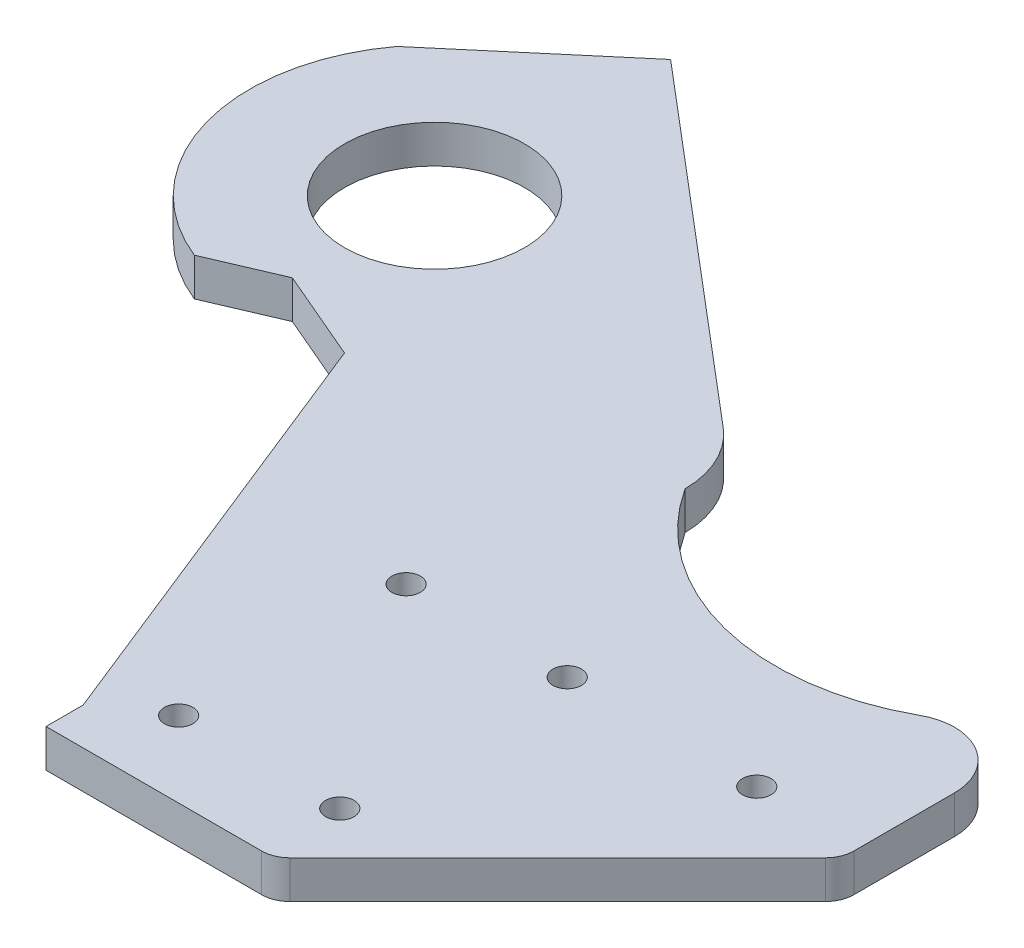
SolidWorks part; units mm, degrees
ref_plane "前视基准面" through (0, 0, 0) normal (0, 0, 1) x (1, 0, 0)
ref_plane "上视基准面" through (0, 0, 0) normal (0, 1, 0) x (1, 0, 0)
ref_plane "右视基准面" through (0, 0, 0) normal (1, 0, 0) x (0, 0, -1)
other "Configuration Table"
sketch "草图2" plane through (0, 0, 0) normal (0, 1, 0) x (1, 0, 0)
  line L0 (0, 0) -> (0, 60)
  line L1 (0, 60) -> (40, 93.9081)
  line L2 (40, 93.9081) -> (80, 60)
  line L3 (80, 60) -> (80, 0)
  line L4 (80, 0) -> (68, 0)
  line L5 (68, 0) -> (68, 42)
  line L6 (68, 42) -> (12, 42) construction
  line L7 (12, 42) -> (12, 0)
  line L8 (12, 0) -> (0, 0)
  line L9 (12, 42) -> (40, 54)
  line L10 (40, 54) -> (68, 42)
  line L11 (40, 93.9081) -> (40, 54) construction
  circle A0 centre (6, 32) radius 1.5
  circle A1 centre (6, 8) radius 1.5
  circle A2 centre (40, 69) radius 9.5
  circle A3 centre (74, 8) radius 1.5
  circle A4 centre (74, 32) radius 1.5
  dimension "D5" = 3
  dimension "D6" = 8
  dimension "D7" = 24
  dimension "D8" = 6
  dimension "D9" = 19
  dimension "D10" = 27
  dimension "D11" = 19
  dimension "D1" = 80
  dimension "D2" = 12
  dimension "D3" = 12
  dimension "D4" = 60
  dimension "D12" = 12
  dimension "D13" = 10
extrude "凸台-拉伸1" add sketch "草图2" along normal blind 4
sketch "草图4" plane through (0, 4, 0) normal (0, 1, 0) x (1, 0, 0)
  line L20 (0, 60) -> (0, 0)
  line L21 (0, 0) -> (12, 0)
  line L22 (12, 0) -> (12, 42)
  line L23 (12, 42) -> (40, 54)
  line L24 (40, 54) -> (68, 42)
  line L25 (68, 42) -> (68, 0)
  line L26 (68, 0) -> (80, 0)
  line L27 (80, 0) -> (80, 60)
  line L28 (80, 60) -> (40, 93.9081)
  line L29 (40, 93.9081) -> (0, 60)
  line L30 (0, 60) -> (0, 0)
  line L31 (0, 0) -> (12, 0)
  line L32 (12, 0) -> (12, 42)
  line L33 (12, 42) -> (40, 54)
  line L34 (40, 54) -> (68, 42)
  line L35 (68, 42) -> (68, 0)
  line L36 (68, 0) -> (80, 0)
  line L37 (80, 0) -> (80, 60)
  line L38 (80, 60) -> (40, 93.9081)
  line L39 (40, 93.9081) -> (0, 60)
  circle A2 centre (40, 69) radius 9.5
  circle A3 centre (40, 69) radius 9.5
  arc A13 (24.3672, 80.6562) -> (32.756, 50.8954) centre (40, 69) ccw
  line M22 (0, 60) -> (0, 0)
  line M24 (0, 0) -> (12, 0)
  line M26 (12, 0) -> (12, 42)
  line M28 (12, 42) -> (40, 54)
  circle M42 centre (6, 32) radius 1.5
  circle M43 centre (6, 8) radius 1.5
  dimension "D3" = 19.5
  dimension "D1" = 0
  dimension "D2" = 0
extrude "切除-拉伸1" cut sketch "草图4" against normal through all contours A13 L39 M22 M24 M26 M28 M42 M43 region at (10.0673, 4, -40.7307)
sketch "草图6" plane through (0, 4, 0) normal (0, 1, 0) x (1, 0, 0)
  line L0 (68, 0) -> (80, 0) construction
  line L1 (80, 60) -> (122, 60)
  line L2 (80, 60) -> (80, 0)
  line L3 (80, 0) -> (122, 0)
  line L4 (122, 60) -> (122, 0)
  circle A0 centre (101, 69) radius 25
  circle A1 centre (40, 69) radius 9.5 construction
  circle A2 centre (40, 69) radius 9.5
  line M13 (80, 0) -> (80, 60)
  dimension "D1" = 50
  dimension "D2" = 42
  dimension "D3" = 21
extrude "凸台-拉伸2" add sketch "草图6" against normal up to surface (4 mm away) contours A0 L1 L3 L4 M13 region at (101, 4, -23.7989) up to face at (53.2241, 0, -47.4242)
sketch "草图7" plane through (0, 4, 0) normal (0, 1, 0) x (1, 0, 0)
  line L0 (101, 69) -> (101, 0) construction
  line L1 (68, 0) -> (122, 0) construction
  circle A0 centre (91, 32) radius 1.5
  circle A1 centre (74, 32) radius 1.5 construction
  circle A2 centre (74, 32) radius 1.5
  circle A3 centre (74, 8) radius 1.5 construction
  circle A4 centre (74, 8) radius 1.5
  circle A6 centre (111, 32) radius 1.5
  circle A7 centre (111, 8) radius 1.5
  circle A8 centre (91, 8) radius 1.5
  point P10 (99.2616, 66.0644)
  point P11 (0, 0)
  point P12 (0, 0)
  point P17 (99.3643, 44.6435)
  point P26 (0, 0)
  dimension "D1" = 10
  dimension "D4" = 17
  dimension "D2" = 2
  dimension "D3" = 2
extrude "切除-拉伸2" cut sketch "草图7" against normal through all
sketch "草图9" plane through (0, 4, 0) normal (0, 1, 0) x (1, 0, 0)
  line L0 (122, 30) -> (92, 0)
  line L1 (122, 55.4353) -> (122, 0) construction
  line L2 (68, 0) -> (122, 0) construction
  line L3 (92, 0) -> (122, 0)
  line L4 (122, 0) -> (122, 30)
  dimension "D1" = 45
  dimension "D2" = 30
extrude "切除-拉伸5" cut sketch "草图9" against normal through all
fillet "圆角4" radius 3 2 edges at (122, 2, -30) (92, 2, 0)
fillet "圆角5" radius 6 1 edges at (122, 2, -55.4353)
fillet "圆角6" radius 10 1 edges at (80, 2, -60)
chamfer "倒角1" distance 20 angle 45 1 edges at (68, 2, -42) first distance on face at (54, 2, -48)
